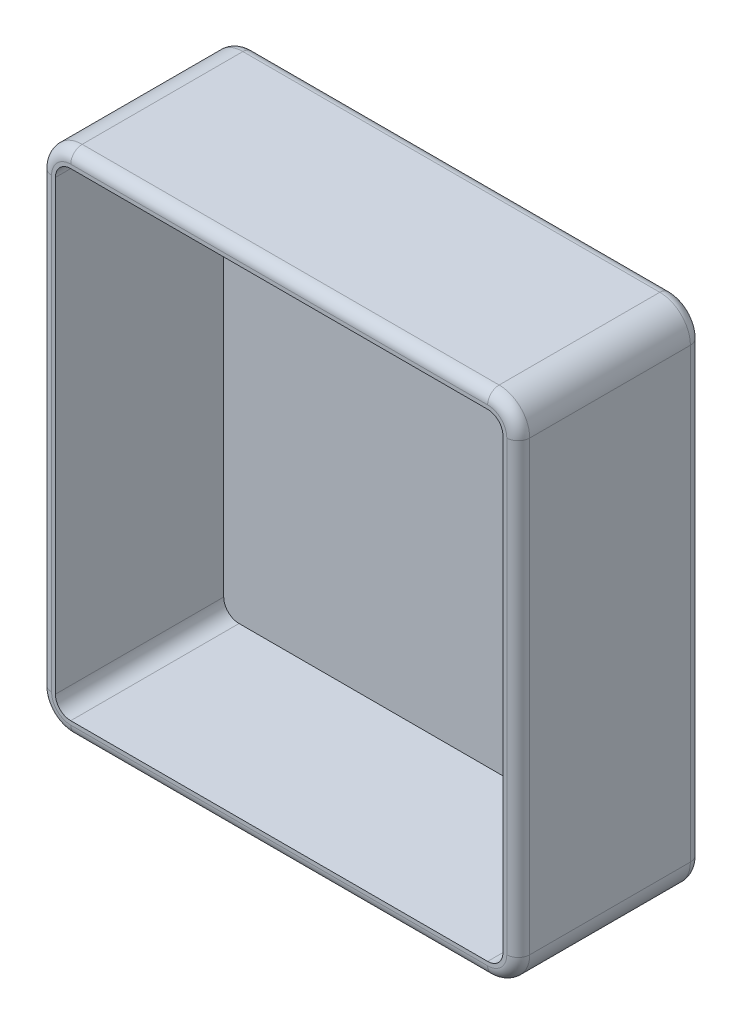
SolidWorks part; units mm, degrees
material "Plastique personnalisé"
ref_plane "Plan de face" through (0, 0, 0) normal (0, 0, 1) x (1, 0, 0)
ref_plane "Plan de dessus" through (0, 0, 0) normal (0, 1, 0) x (1, 0, 0)
ref_plane "Plan de droite" through (0, 0, 0) normal (1, 0, 0) x (0, 0, -1)
sketch "Esquisse1" plane through (0, 0, 0) normal (0, 0, 1) x (1, 0, 0)
  line L1 (2, 0) -> (56.5, 0)
  line L2 (0, 2) -> (0, 60.5)
  line L3 (2, 62.5) -> (56.5, 62.5)
  line L4 (58.5, 2) -> (58.5, 60.5)
  arc A0 (56.5, 0) -> (58.5, 2) centre (56.5, 2) ccw
  arc A1 (2, 0) -> (0, 2) centre (2, 2) cw
  arc A2 (0, 60.5) -> (2, 62.5) centre (2, 60.5) cw
  arc A3 (56.5, 62.5) -> (58.5, 60.5) centre (56.5, 60.5) cw
  point P7 (58.5, 0)
  point P10 (0, 0)
  point P13 (0, 62.5)
  point P16 (58.5, 62.5)
  dimension "D3" = 2
  dimension "D1" = 58.5
  dimension "D2" = 62.5
extrude "Boss.-Extru.1" add sketch "Esquisse1" along normal blind 22
shell "Coque1" thickness 2 removed face at (29.25, 31.25, 22) outward yes
fillet "Congé1" radius 1.5 8 edges at (-0.8284, -0.8284, 22) (-2, 31.25, 22) (-0.8284, 63.3284, 22) (29.25, 64.5, 22) (59.3284, 63.3284, 22) (60.5, 31.25, 22) (59.3284, -0.8284, 22) (29.25, -2, 22)
fillet "Congé2" radius 1.5 8 edges at (-0.8284, -0.8284, -2) (-2, 31.25, -2) (-0.8284, 63.3284, -2) (29.25, 64.5, -2) (59.3284, 63.3284, -2) (60.5, 31.25, -2) (59.3284, -0.8284, -2) (29.25, -2, -2)
